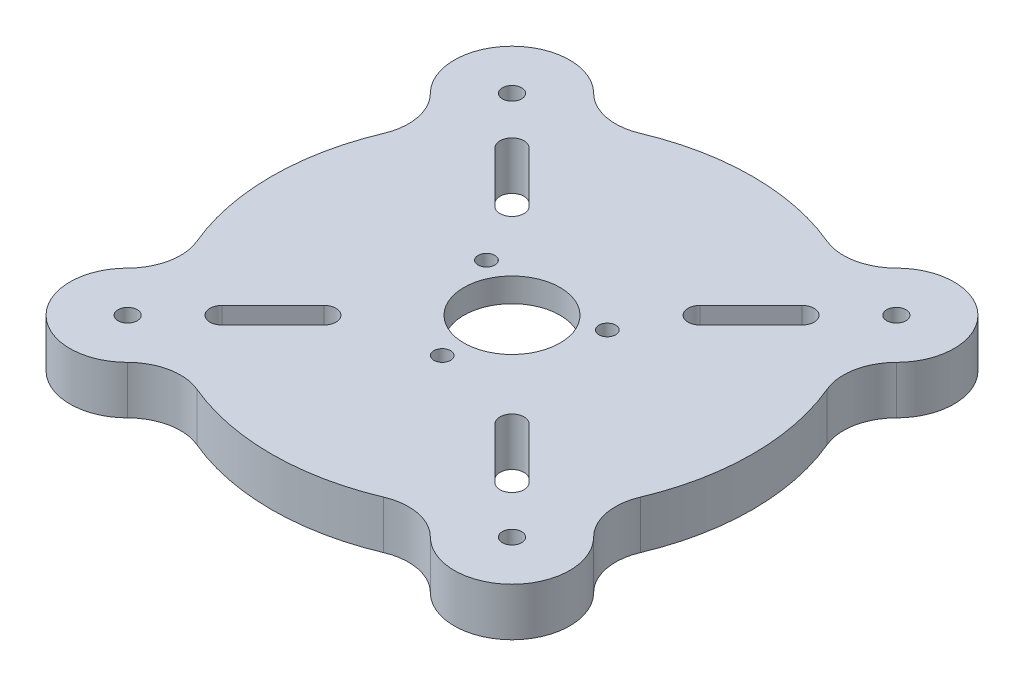
SolidWorks part; units mm, degrees
ref_plane "Front Plane" through (0, 0, 0) normal (0, 0, 1) x (1, 0, 0)
ref_plane "Top Plane" through (0, 0, 0) normal (0, 1, 0) x (1, 0, 0)
ref_plane "Right Plane" through (0, 0, 0) normal (1, 0, 0) x (0, 0, -1)
sketch "Sketch1" plane through (0, 0, 0) normal (0, 1, 0) x (1, 0, 0)
  line L0 (-39.9515, -39.9515) -> (39.9515, 39.9515) construction
  line L1 (-48.4368, -31.4663) -> (31.4663, 48.4368) construction
  line L2 (-31.4663, -48.4368) -> (48.4368, 31.4663) construction
  line L3 (0, 0) -> (0, 50) construction
  line L4 (39.9515, -39.9515) -> (-39.9515, 39.9515) construction
  line L5 (48.4368, -31.4663) -> (-31.4663, 48.4368) construction
  line L6 (31.4663, -48.4368) -> (-48.4368, 31.4663) construction
  line L7 (19.5467, 19.5467) -> (30.1533, 30.1533) construction
  line L8 (17.7789, 21.3144) -> (28.3855, 31.921)
  line L9 (21.3144, 17.7789) -> (31.921, 28.3855)
  line L10 (17.7789, -21.3144) -> (28.3855, -31.921)
  line L11 (21.3144, -17.7789) -> (31.921, -28.3855)
  line L12 (19.5467, -19.5467) -> (30.1533, -30.1533) construction
  line L13 (-21.3144, -17.7789) -> (-31.921, -28.3855)
  line L14 (-17.7789, -21.3144) -> (-28.3855, -31.921)
  line L15 (-19.5467, -19.5467) -> (-30.1533, -30.1533) construction
  line L16 (-17.7789, 21.3144) -> (-28.3855, 31.921)
  line L17 (-21.3144, 17.7789) -> (-31.921, 28.3855)
  line L18 (-19.5467, 19.5467) -> (-30.1533, 30.1533) construction
  circle A0 centre (0, 0) radius 50
  arc A1 (-48.4368, -31.4663) -> (-31.4663, -48.4368) centre (-39.9515, -39.9515) ccw construction
  arc A2 (48.4368, 31.4663) -> (31.4663, 48.4368) centre (39.9515, 39.9515) ccw construction
  arc A3 (48.4368, -31.4663) -> (31.4663, -48.4368) centre (39.9515, -39.9515) cw construction
  arc A4 (-48.4368, 31.4663) -> (-31.4663, 48.4368) centre (-39.9515, 39.9515) cw construction
  arc A5 (19.4135, 46.0773) -> (31.4663, 48.4368) centre (23.6858, 56.2173) ccw
  arc A6 (48.4368, 31.4663) -> (46.0773, 19.4135) centre (56.2173, 23.6858) ccw
  arc A7 (17.7789, 21.3144) -> (21.3144, 17.7789) centre (19.5467, 19.5467) ccw
  arc A8 (31.921, 28.3855) -> (28.3855, 31.921) centre (30.1533, 30.1533) ccw
  circle A9 centre (39.9515, 39.9515) radius 2
  arc A10 (31.4663, 48.4368) -> (48.4368, 31.4663) centre (39.9515, 39.9515) cw
  arc A11 (48.4368, -31.4663) -> (31.4663, -48.4368) centre (39.9515, -39.9515) cw
  arc A12 (46.0773, -19.4135) -> (48.4368, -31.4663) centre (56.2173, -23.6858) ccw
  arc A13 (31.4663, -48.4368) -> (19.4135, -46.0773) centre (23.6858, -56.2173) ccw
  circle A14 centre (39.9515, -39.9515) radius 2
  arc A15 (21.3144, -17.7789) -> (17.7789, -21.3144) centre (19.5467, -19.5467) ccw
  arc A16 (28.3855, -31.921) -> (31.921, -28.3855) centre (30.1533, -30.1533) ccw
  arc A17 (-31.4663, -48.4368) -> (-48.4368, -31.4663) centre (-39.9515, -39.9515) cw
  arc A18 (-19.4135, -46.0773) -> (-31.4663, -48.4368) centre (-23.6858, -56.2173) ccw
  arc A19 (-48.4368, -31.4663) -> (-46.0773, -19.4135) centre (-56.2173, -23.6858) ccw
  circle A20 centre (-39.9515, -39.9515) radius 2
  arc A21 (-17.7789, -21.3144) -> (-21.3144, -17.7789) centre (-19.5467, -19.5467) ccw
  arc A22 (-31.921, -28.3855) -> (-28.3855, -31.921) centre (-30.1533, -30.1533) ccw
  arc A23 (-48.4368, 31.4663) -> (-31.4663, 48.4368) centre (-39.9515, 39.9515) cw
  arc A24 (-46.0773, 19.4135) -> (-48.4368, 31.4663) centre (-56.2173, 23.6858) ccw
  arc A25 (-31.4663, 48.4368) -> (-19.4135, 46.0773) centre (-23.6858, 56.2173) ccw
  circle A26 centre (-39.9515, 39.9515) radius 2
  arc A27 (-21.3144, 17.7789) -> (-17.7789, 21.3144) centre (-19.5467, 19.5467) ccw
  arc A28 (-28.3855, 31.921) -> (-31.921, 28.3855) centre (-30.1533, 30.1533) ccw
  point P5 (0, 0)
  point P13 (0, 0)
  point P26 (24.85, 24.85)
  point P45 (24.85, -24.85)
  point P61 (-24.85, -24.85)
  point P77 (-24.85, 24.85)
  point P85 (0, 0)
  dimension "D1" = 100
  dimension "D2" = 12
  dimension "D5" = 2.5
  dimension "D7" = 4
  dimension "D3" = 113
  dimension "D4" = 45
  dimension "D6" = 15
  dimension "D8" = 4
extrude "Boss-Extrude1" add sketch "Sketch1" along normal blind 10 contours A0 A28 L16 A27 L17 A22 L13 A21 L14 A16 L10 A15 L11 A8 L9 A7 L8 | A25 A23 A24 A0 A26 | A19 A17 A18 A0 A20 | A13 A11 A12 A0 A14 | A10 A5 A0 A6 A9 region at (0, 0, 0) region at (35.6807, 0, -35.6807) region at (44.9674, 0, 25.8881) region at (-35.6807, 0, -35.6807) region at (-25.8881, 0, 44.9674)
sketch "Sketch3" plane through (0, 0, 0) normal (0, -1, 0) x (1, 0, 0)
  circle A0 centre (0, 0) radius 21
  circle A1 centre (0, 14.5) radius 1.75
  circle A2 centre (12.5574, -7.25) radius 1.75
  circle A3 centre (-12.5574, -7.25) radius 1.75
  circle A4 centre (0, 0) radius 10
  point P12 (0, 0)
  dimension "D1" = 3.5
  dimension "D4" = 42
  dimension "D2" = 14.5
  dimension "D3" = 3
extrude "Cut-Extrude2" cut sketch "Sketch3" against normal blind 5 contours A0
extrude "Cut-Extrude3" cut sketch "Sketch3<4>" against normal through all contours A3 | A2 | A1
sketch "Sketch3<4>" plane through (0, 0, 0) normal (0, -1, 0) x (1, 0, 0) same geometry as "Sketch3"
extrude "Cut-Extrude4" cut sketch "Sketch3<5>" against normal through all contours A4
sketch "Sketch3<5>" plane through (0, 0, 0) normal (0, -1, 0) x (1, 0, 0) same geometry as "Sketch3"
